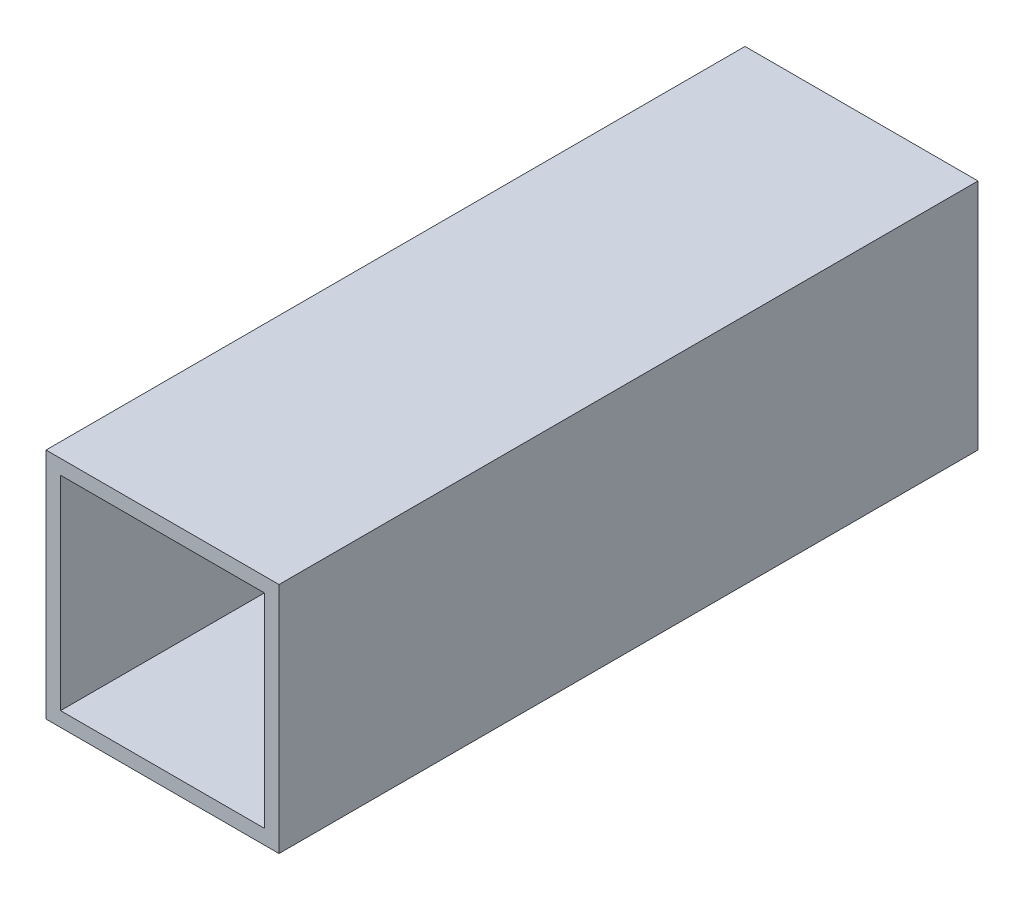
SolidWorks part; units mm, degrees
material "6061-T6 (SS)"
ref_plane "Front Plane" through (0, 0, 0) normal (0, 0, 1) x (1, 0, 0)
ref_plane "Top Plane" through (0, 0, 0) normal (0, 1, 0) x (1, 0, 0)
ref_plane "Right Plane" through (0, 0, 0) normal (1, 0, 0) x (0, 0, -1)
sketch "Sketch1" plane through (0, 0, 0) normal (0, 0, 1) x (1, 0, 0)
  line L1 (-12.7, -12.7) -> (12.7, -12.7)
  line L2 (-12.7, -12.7) -> (-12.7, 12.7)
  line L3 (-12.7, 12.7) -> (12.7, 12.7)
  line L4 (12.7, -12.7) -> (12.7, 12.7)
  line L5 (-12.7, -12.7) -> (12.7, 12.7) construction
  line L6 (-12.7, 12.7) -> (12.7, -12.7) construction
  point P0 (0, 0)
  dimension "D1" = 25.4
extrude "Boss-Extrude1" add sketch "Sketch1" along normal mid plane 76.2
shell "Shell1" thickness 1.5875 removed face at (0, 0, -38.1) removed face at (0, 0, 38.1)
